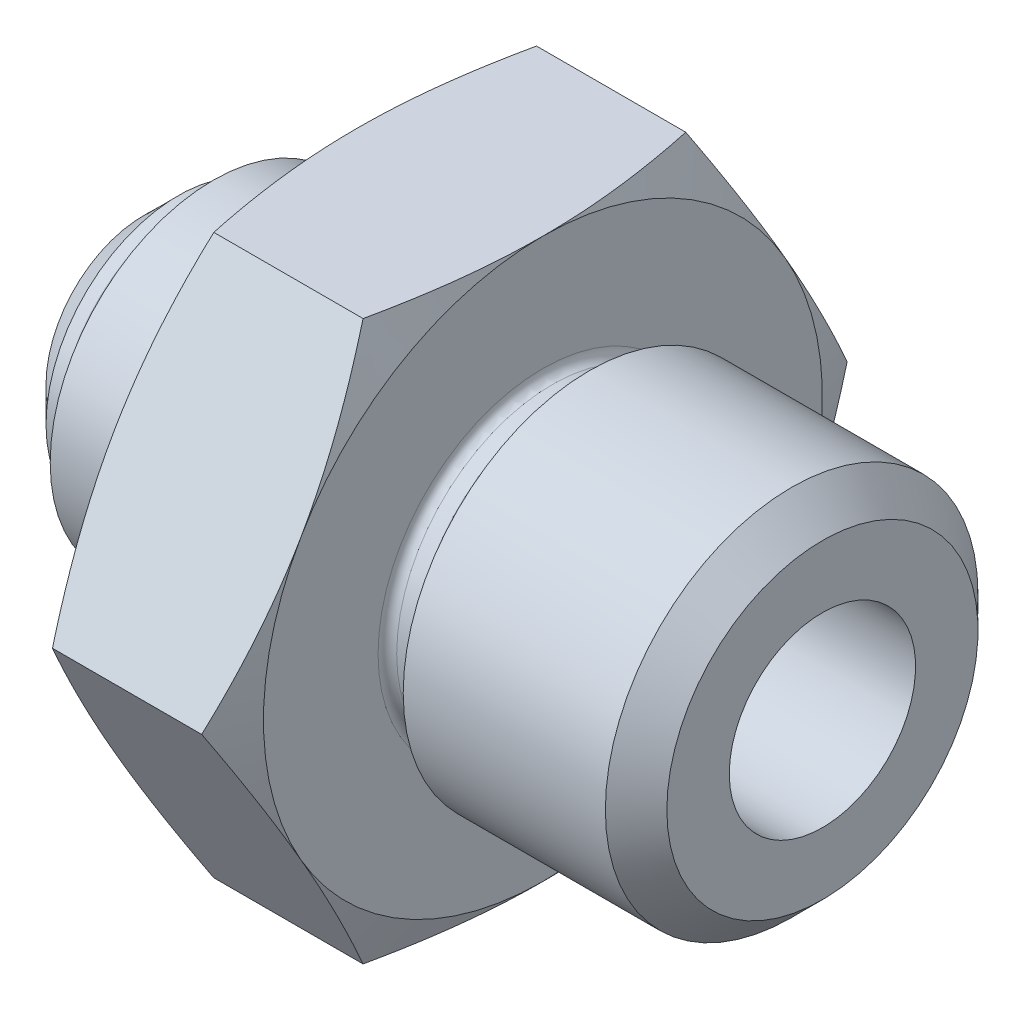
SolidWorks part; units mm, degrees
material "Plain Carbon Steel"
ref_plane "Front" through (0, 0, 0) normal (0, 0, 1) x (1, 0, 0)
ref_plane "Top" through (0, 0, 0) normal (0, 1, 0) x (1, 0, 0)
ref_plane "Right" through (0, 0, 0) normal (1, 0, 0) x (0, 0, -1)
ref_axis "Axis1" through (-84.4107, 0, 0) along (1, 0, 0)
ref_axis "Axis2" through (0, 64.3378, 0) along (0, -1, 0)
ref_axis "Axis3" through (0, 0, -102.329) along (0, 0, 1)
sketch "Sketch1" plane through (0, 0, 0) normal (0, 1, 0) x (1, 0, 0)
  line L0 (6.5006, 7.08) -> (6.5006, 12)
  line L1 (-10.6368, 4) -> (18.5006, 4)
  line L2 (-10.6368, 4) -> (-10.6368, 4.2)
  line L3 (1.5006, 19) -> (3.5006, 19)
  line L4 (18.5006, 4) -> (18.5006, 6.68)
  line L5 (-10.6368, 4.2) -> (-9.1565, 5.6803)
  line L6 (-8.6187, 5.6803) -> (-9.1565, 5.6803)
  line L7 (6.9006, 6.68) -> (7.5475, 6.68)
  line L8 (18.5006, 6.68) -> (17.1806, 8)
  line L9 (-8.367, 5.7695) -> (-7.6565, 7)
  line L10 (-1.4994, 12) -> (-1.4994, 6.0803)
  line L11 (-1.8994, 5.6803) -> (-2.5446, 5.6803)
  line L12 (-7.6565, 7) -> (-3.4994, 7)
  line L13 (-2.7831, 5.7592) -> (-3.4994, 7)
  line L14 (-1.4994, 12) -> (1.5006, 19)
  line L15 (7.9453, 7.0383) -> (8.5006, 8)
  line L16 (8.5006, 8) -> (17.1806, 8)
  line L17 (6.5006, 12) -> (3.5006, 19)
  arc A0 (-8.367, 5.7695) -> (-8.6187, 5.6803) centre (-8.6187, 6.0803) cw
  arc A1 (-2.7831, 5.7592) -> (-2.5446, 5.6803) centre (-2.5446, 6.0803) ccw
  arc A2 (-1.4994, 6.0803) -> (-1.8994, 5.6803) centre (-1.8994, 6.0803) cw
  arc A3 (6.5006, 7.08) -> (6.9006, 6.68) centre (6.9006, 7.08) ccw
  arc A4 (7.5475, 6.68) -> (7.9453, 7.0383) centre (7.5475, 7.08) ccw
  point P20 (-8.4184, 5.6803)
  dimension "D1" = 45
  dimension "D6" = 3
  dimension "D9" = 0.4
  dimension "D2" = 120
  dimension "D3" = 120
  dimension "D4" = 120
  dimension "D5" = 135
  dimension "D7" = 3
  dimension "D8" = 12
  dimension "D10" = 12
  dimension "D11" = 8
  dimension "D12" = 2
  dimension "D13" = 1.5
  dimension "D14" = 0.2
  dimension "D15" = 8
  dimension "D16" = 1.3197
  dimension "D17" = 15
  dimension "D18" = 2
  dimension "D19" = 1.32
  dimension "D20" = 7
  dimension "D21" = 4
revolve "Revolve1" add sketch "Sketch1" angle 360 about axis through (-84.4107, 0, 0) along (1, 0, 0)
sketch "Sketch2" plane through (-1.4994, 0, 0) normal (-1, 0, 0) x (0, 0, 1)
  line L0 (-14.7309, 12) -> (14.7309, 12)
  circle A0 centre (0, 0) radius 19 construction
  dimension "D1" = 12
extrude "Cut-Extrude1" cut sketch "Sketch2" against normal through all and the other way through all
pattern_circular "CirPattern1" count 6 over 360 about axis through (-84.4107, 0, 0) along (1, 0, 0) of "Cut-Extrude1"
